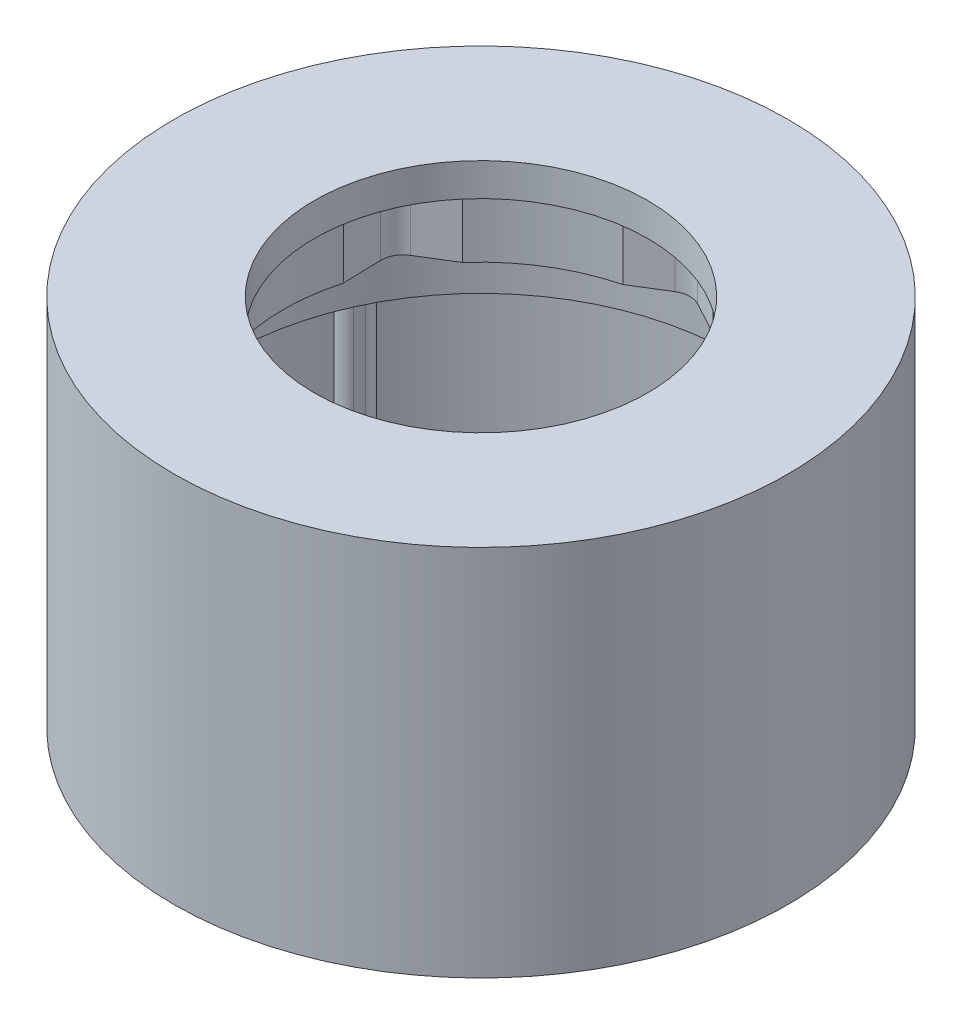
SolidWorks part; units mm, degrees
material "ABS"
ref_plane "Спереди" through (0, 0, 0) normal (0, 0, 1) x (1, 0, 0)
ref_plane "Сверху" through (0, 0, 0) normal (0, 1, 0) x (1, 0, 0)
ref_plane "Справа" through (0, 0, 0) normal (1, 0, 0) x (0, 0, -1)
sketch "Эскиз1" plane through (0, 0, 0) normal (0, 0, 1) x (1, 0, 0)
  line L0 (0, 0) -> (0, 194.0667) construction
  line L1 (7.6, 118.6429) -> (14, 118.6429)
  line L2 (14, 118.6429) -> (14, 101.6429)
  line L3 (14, 101.6429) -> (9, 101.6429)
  line L4 (9, 101.6429) -> (9, 117.1429)
  line L5 (9, 117.1429) -> (7.6, 117.1429)
  line L6 (7.6, 117.1429) -> (7.6, 118.6429)
  dimension "D1" = 7.6
  dimension "D2" = 14
  dimension "D3" = 1.5
  dimension "D4" = 5
  dimension "D5" = 17
revolve "Повернуть1" add sketch "Эскиз1" angle 360 about L0
sketch "Эскиз2" plane through (0, 101.6429, 0) normal (0, -1, 0) x (1, 0, 0)
  line L1 (0.2818, 9.9264) -> (-8.4557, 5.2072)
  line L2 (-8.4557, 5.2072) -> (-8.7374, -4.7192)
  line L3 (-8.7374, -4.7192) -> (-0.2818, -9.9264)
  line L4 (-0.2818, -9.9264) -> (8.4557, -5.2072)
  line L5 (8.4557, -5.2072) -> (8.7374, 4.7192)
  line L6 (8.7374, 4.7192) -> (0.2818, 9.9264)
  circle A0 centre (0, 0) radius 8.6 construction
  dimension "D1" = 17.2
extrude "Вырез-Вытянуть1" cut sketch "Эскиз2" against normal up to surface (15.5 mm away) contours L2 L3 L4 L5 L6 L1 up to face at (0, 117.1429, -9)
sketch "Эскиз4" plane through (0, 101.6429, 0) normal (0, -1, 0) x (1, 0, 0)
  circle A0 centre (0, 0) radius 11.5
  dimension "D1" = 23
extrude "Вырез-Вытянуть9" cut sketch "Эскиз4" against normal blind 12
sketch "Эскиз5" plane through (0, 101.6429, 0) normal (0, -1, 0) x (1, 0, 0)
  line L0 (0, 12.6) -> (0, 13.1)
  line L1 (10.9119, 6.3) -> (11.3449, 6.55)
  line L2 (1.365, 12.5258) -> (1.4192, 13.0229)
  line L3 (11.5302, 5.0808) -> (11.9878, 5.2824)
  line L4 (10.9119, -6.3) -> (11.3449, -6.55)
  line L5 (10.1652, -7.4451) -> (10.5686, -7.7405)
  line L6 (0, -12.6) -> (0, -13.1)
  line L7 (-1.365, -12.5258) -> (-1.4192, -13.0229)
  line L8 (-10.9119, -6.3) -> (-11.3449, -6.55)
  line L9 (-11.5302, -5.0808) -> (-11.9878, -5.2824)
  line L10 (-10.9119, 6.3) -> (-11.3449, 6.55)
  line L11 (-10.1652, 7.4451) -> (-10.5686, 7.7405)
  circle A0 centre (0, 0) radius 12.6 construction
  circle A1 centre (0, 0) radius 13.1 construction
  arc A2 (0, 12.6) -> (1.365, 12.5258) centre (0, 0) cw
  arc A3 (10.9119, 6.3) -> (11.5302, 5.0808) centre (0, 0) cw
  arc A4 (10.9119, -6.3) -> (10.1652, -7.4451) centre (0, 0) cw
  arc A5 (0, -12.6) -> (-1.365, -12.5258) centre (0, 0) cw
  arc A6 (-10.9119, -6.3) -> (-11.5302, -5.0808) centre (0, 0) cw
  arc A7 (-10.9119, 6.3) -> (-10.1652, 7.4451) centre (0, 0) cw
  arc A8 (0, 13.1) -> (-10.5686, 7.7405) centre (0, 0) ccw
  arc A9 (11.3449, 6.55) -> (1.4192, 13.0229) centre (0, 0) ccw
  arc A10 (11.3449, -6.55) -> (11.9878, 5.2824) centre (0, 0) ccw
  arc A11 (0, -13.1) -> (10.5686, -7.7405) centre (0, 0) ccw
  arc A12 (-11.3449, -6.55) -> (-1.4192, -13.0229) centre (0, 0) ccw
  arc A13 (-11.3449, 6.55) -> (-11.9878, -5.2824) centre (0, 0) ccw
  point P32 (0, 0)
  point P44 (0, 0)
  dimension "D1" = 25.2
  dimension "D2" = 26.2
  dimension "D3" = 6
  dimension "D4" = 6
extrude "Вырез-Вытянуть10" cut sketch "Эскиз5" against normal blind 9
fillet "Скругление1" radius 1 6 edges at (0.2818, 115.3929, 9.9264) (-8.4557, 115.3929, 5.2072) (8.7374, 115.3929, 4.7192) (8.4557, 115.3929, -5.2072) (-8.7374, 115.3929, -4.7192) (-0.2818, 115.3929, -9.9264)
fillet "Скругление2" radius 0.5 12 edges at (10.1652, 106.1429, -7.4451) (10.9119, 106.1429, -6.3) (-1.365, 106.1429, -12.5258) (0, 106.1429, -12.6) (-10.9119, 106.1429, -6.3) (-11.5302, 106.1429, -5.0808) (-10.1652, 106.1429, 7.4451) (-10.9119, 106.1429, 6.3) (11.5302, 106.1429, 5.0808) (10.9119, 106.1429, 6.3) (1.365, 106.1429, 12.5258) (0, 106.1429, 12.6)
chamfer "Фаска1" distance 0.5 angle 72 30 edges at (10.5647, 101.6429, -7.7377) (11.3408, 101.6429, -6.5476) (10.3637, 101.6429, -7.4172) (10.9665, 101.6429, -6.4929) (10.5541, 101.6429, -6.8827) (-1.4187, 101.6429, -13.0182) (0, 101.6429, -13.0952) (-1.2416, 101.6429, -12.6839) (-0.1398, 101.6429, -12.7437) (-0.6835, 101.6429, -12.5814) (-11.9834, 101.6429, -5.2805) (-11.3408, 101.6429, -6.5476) (-11.6054, 101.6429, -5.2666) (-11.1063, 101.6429, -6.2508) (-11.2376, 101.6429, -5.6988) (11.9834, 101.6429, 5.2805) (11.3408, 101.6429, 6.5476) (11.6054, 101.6429, 5.2666) (11.1063, 101.6429, 6.2508) (11.2376, 101.6429, 5.6988) (1.4187, 101.6429, 13.0182) (0, 101.6429, 13.0952) (1.2416, 101.6429, 12.6839) (0.1398, 101.6429, 12.7437) (0.6835, 101.6429, 12.5814) (-10.5647, 101.6429, 7.7377) (-11.3408, 101.6429, 6.5476) (-10.3637, 101.6429, 7.4172) (-10.9665, 101.6429, 6.4929) (-10.5541, 101.6429, 6.8827) first distance on face at (0, 101.6429, 0)
